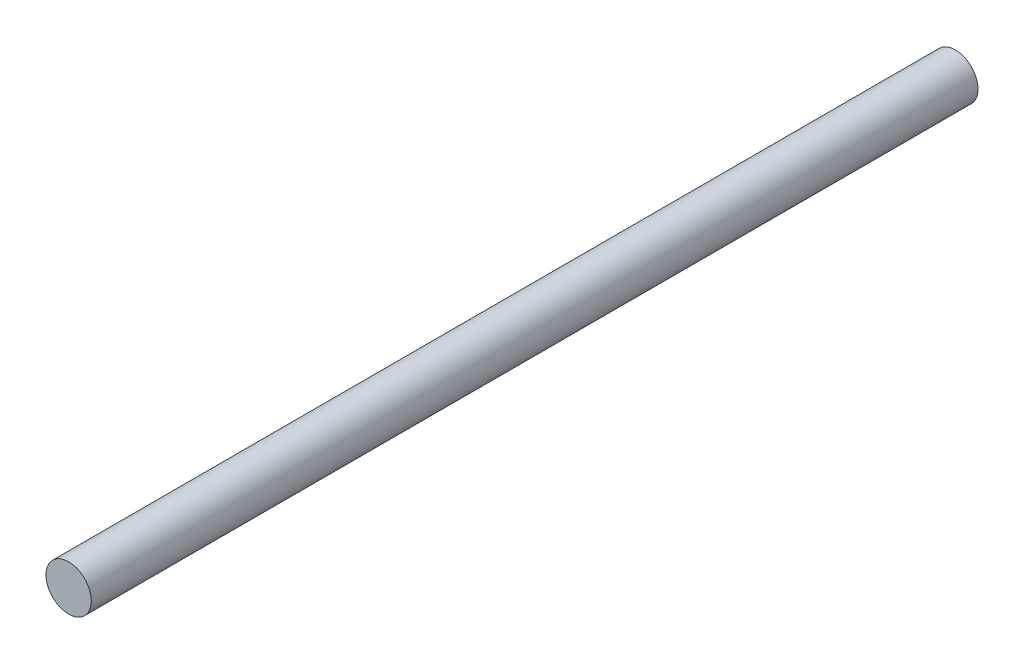
SolidWorks part; units mm, degrees
material "1060 Alloy"
ref_plane "Płaszczyzna przednia" through (0, 0, 0) normal (0, 0, 1) x (1, 0, 0)
ref_plane "Płaszczyzna górna" through (0, 0, 0) normal (0, 1, 0) x (1, 0, 0)
ref_plane "Płaszczyzna prawa" through (0, 0, 0) normal (1, 0, 0) x (0, 0, -1)
sketch "Sketch1" plane through (0, 0, 0) normal (0, 0, 1) x (1, 0, 0)
  circle A0 centre (0, 0) radius 5
  dimension "D1" = 10
extrude "Boss-Extrude1" add sketch "Sketch1" along normal blind 195.6
